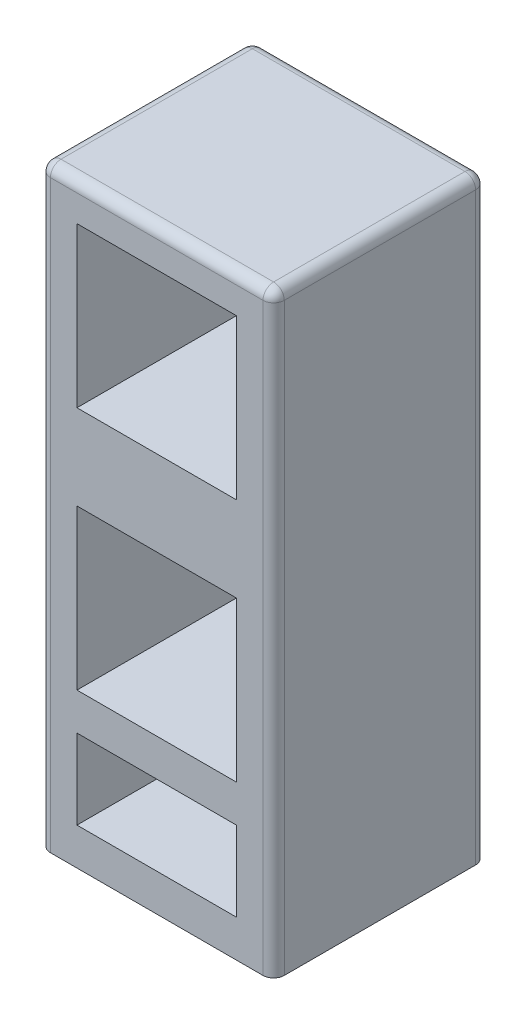
SolidWorks part; units mm, degrees
ref_plane "Front Plane" through (0, 0, 0) normal (0, 0, 1) x (1, 0, 0)
ref_plane "Top Plane" through (0, 0, 0) normal (0, 1, 0) x (1, 0, 0)
ref_plane "Right Plane" through (0, 0, 0) normal (1, 0, 0) x (0, 0, -1)
sketch "Sketch1" plane through (0, 0, 0) normal (0, 0, 1) x (1, 0, 0)
  line L1 (-25.0962, 42.3339) -> (-3.0962, 42.3339)
  line L2 (-25.0962, 42.3339) -> (-25.0962, -13.6661)
  line L3 (-25.0962, -13.6661) -> (-3.0962, -13.6661)
  line L4 (-3.0962, 42.3339) -> (-3.0962, -13.6661)
  line L5 (-21.5962, 38.8339) -> (-6.5962, 38.8339)
  line L6 (-21.5962, 38.8339) -> (-21.5962, 23.8339)
  line L7 (-21.5962, 23.8339) -> (-6.5962, 23.8339)
  line L8 (-6.5962, 38.8339) -> (-6.5962, 23.8339)
  dimension "D1" = 22
  dimension "D2" = 56
  dimension "D3" = 15
  dimension "D4" = 3.5
  dimension "D5" = 3.5
  dimension "D6" = 15
extrude "Boss-Extrude1" add sketch "Sketch1" along normal blind 20
sketch "Sketch2" plane through (0, 0, 20) normal (0, 0, 1) x (1, 0, 0)
  line L0 (-3.0962, -13.6661) -> (-3.0962, 42.3339) construction
  line L1 (-21.5962, 15.8339) -> (-6.5962, 15.8339)
  line L2 (-21.5962, 15.8339) -> (-21.5962, 0.8339)
  line L3 (-21.5962, 0.8339) -> (-6.5962, 0.8339)
  line L4 (-6.5962, 15.8339) -> (-6.5962, 0.8339)
  line L5 (-21.5962, 23.8339) -> (-6.5962, 23.8339) construction
  line L6 (-25.0962, -13.6661) -> (-3.0962, -13.6661) construction
  line L7 (-21.5962, -2.6661) -> (-6.5962, -2.6661)
  line L8 (-21.5962, -2.6661) -> (-21.5962, -10.1661)
  line L9 (-21.5962, -10.1661) -> (-6.5962, -10.1661)
  line L10 (-6.5962, -2.6661) -> (-6.5962, -10.1661)
  dimension "D1" = 15
  dimension "D2" = 3.5
  dimension "D3" = 8
  dimension "D4" = 15
  dimension "D5" = 15
  dimension "D6" = 3.5
  dimension "D7" = 3.5
extrude "Cut-Extrude1" cut sketch "Sketch2" against normal offset from surface (15.5 mm away) 4.5 up to face at (-14.0962, 14.3339, 0)
fillet "Fillet1" radius 1 8 edges at (-14.0962, 42.3339, 0) (-14.0962, 42.3339, 20) (-3.0962, 42.3339, 10) (-3.0962, 14.3339, 0) (-3.0962, 14.3339, 20) (-25.0962, 14.3339, 0) (-25.0962, 14.3339, 20) (-25.0962, 42.3339, 10)
